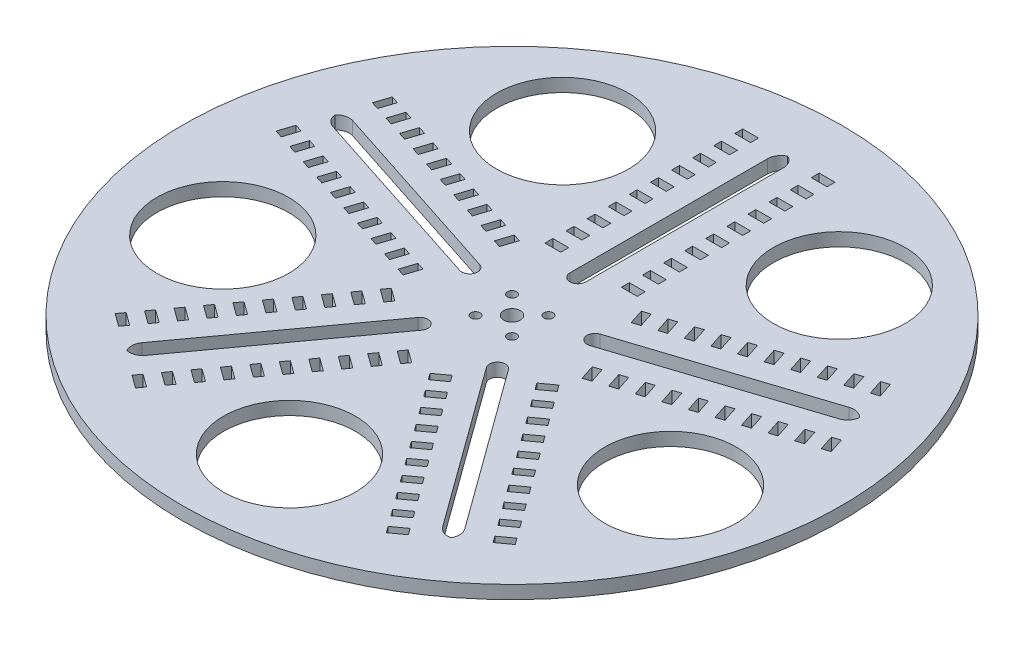
SolidWorks part; units mm, degrees
material "PVC rígido"
ref_plane "Alzado" through (0, 0, 0) normal (0, 0, 1) x (1, 0, 0)
ref_plane "Planta" through (0, 0, 0) normal (0, 1, 0) x (1, 0, 0)
ref_plane "Vista lateral" through (0, 0, 0) normal (1, 0, 0) x (0, 0, -1)
sketch "Croquis1" plane through (0, 0, 0) normal (0, 1, 0) x (1, 0, 0)
  circle A0 centre (0, 0) radius 125
  dimension "D1" = 250
extrude "Saliente-Extruir1" add sketch "Croquis1" along normal blind 5
sketch "Croquis2" plane through (0, 5, 0) normal (0, 1, 0) x (1, 0, 0)
  circle A0 centre (0, 0) radius 3.15
  dimension "D1" = 6.3
extrude "Cortar-Extruir1" cut sketch "Croquis2" against normal through all
sketch "Croquis3" plane through (0, 5, 0) normal (0, 1, 0) x (1, 0, 0)
  line L0 (0, 125) -> (0, -125) construction
  line L1 (-125, 0) -> (125, 0) construction
  line L2 (0, 105) -> (0, 25) construction
  line L3 (3, 105) -> (3, 25)
  line L4 (-3, 105) -> (-3, 25)
  line L5 (99.8609, 32.4468) -> (23.7764, 7.7254) construction
  line L6 (100.788, 29.5936) -> (24.7035, 4.8723)
  line L7 (98.9339, 35.3) -> (22.8494, 10.5786)
  line L8 (61.7175, -84.9468) -> (14.6946, -20.2254) construction
  line L9 (59.2904, -86.7101) -> (12.2676, -21.9888)
  line L10 (64.1445, -83.1834) -> (17.1217, -18.4621)
  line L11 (-61.7175, -84.9468) -> (-14.6946, -20.2254) construction
  line L12 (-64.1445, -83.1834) -> (-17.1217, -18.4621)
  line L13 (-59.2904, -86.7101) -> (-12.2676, -21.9888)
  line L14 (-99.8609, 32.4468) -> (-23.7764, 7.7254) construction
  line L15 (-98.9339, 35.3) -> (-22.8494, 10.5786)
  line L16 (-100.788, 29.5936) -> (-24.7035, 4.8723)
  circle A0 centre (0, 0) radius 105
  circle A1 centre (0, 0) radius 125 construction
  arc A2 (3, 105) -> (-3, 105) centre (0, 105) ccw
  arc A3 (-3, 25) -> (3, 25) centre (0, 25) ccw
  arc A4 (100.788, 29.5936) -> (98.9339, 35.3) centre (99.8609, 32.4468) ccw
  arc A5 (22.8494, 10.5786) -> (24.7035, 4.8723) centre (23.7764, 7.7254) ccw
  arc A6 (59.2904, -86.7101) -> (64.1445, -83.1834) centre (61.7175, -84.9468) ccw
  arc A7 (17.1217, -18.4621) -> (12.2676, -21.9888) centre (14.6946, -20.2254) ccw
  arc A8 (-64.1445, -83.1834) -> (-59.2904, -86.7101) centre (-61.7175, -84.9468) ccw
  arc A9 (-12.2676, -21.9888) -> (-17.1217, -18.4621) centre (-14.6946, -20.2254) ccw
  arc A10 (-98.9339, 35.3) -> (-100.788, 29.5936) centre (-99.8609, 32.4468) ccw
  arc A11 (-24.7035, 4.8723) -> (-22.8494, 10.5786) centre (-23.7764, 7.7254) ccw
  point P12 (0, 65)
  point P22 (61.8187, 20.0861)
  point P29 (38.206, -52.5861)
  point P36 (-38.206, -52.5861)
  point P43 (-61.8187, 20.0861)
  point P48 (0, 0)
  dimension "D1" = 210
  dimension "D3" = 3
  dimension "D2" = 80
  dimension "D4" = 5
extrude "Cortar-Extruir2" cut sketch "Croquis3" against normal through all contours L4 A3 L3 A0 | L7 A5 L6 A0 | L10 A7 L9 A0 | L13 A9 L12 A0 | L16 A11 L15 A0 region at (0, 5, -63.812) region at (60.6889, 5, -19.719) region at (-60.6889, 5, -19.719) region at (37.5078, 5, 51.625) region at (-37.5078, 5, 51.625)
sketch "Croquis5" plane through (0, 5, 0) normal (0, 1, 0) x (1, 0, 0)
  line L0 (0, 125) -> (0, -125) construction
  line L1 (-60.6817, 105) -> (53.5171, 105) construction
  line L2 (91.6, 48.1632) -> (93.4541, 42.4569)
  line L3 (-17.5, 105) -> (-11.5, 105)
  line L4 (-17.5, 105) -> (-17.5, 102)
  line L5 (-17.5, 102) -> (-11.5, 102)
  line L6 (-11.5, 105) -> (-11.5, 102)
  line L7 (11.5, 105) -> (17.5, 105)
  line L8 (11.5, 105) -> (11.5, 102)
  line L9 (11.5, 102) -> (17.5, 102)
  line L10 (17.5, 105) -> (17.5, 102)
  line L11 (100.5615, 20.5826) -> (102.4156, 14.8762)
  line L12 (94.4531, 49.0903) -> (91.6, 48.1632)
  line L13 (94.4531, 49.0903) -> (96.3072, 43.3839)
  line L14 (96.3072, 43.3839) -> (93.4541, 42.4569)
  line L15 (103.4146, 21.5096) -> (100.5615, 20.5826)
  line L16 (103.4146, 21.5096) -> (105.2687, 15.8033)
  line L17 (105.2687, 15.8033) -> (102.4156, 14.8762)
  line L18 (74.1119, -72.2335) -> (69.2578, -75.7602)
  line L19 (50.6504, -89.2793) -> (45.7963, -92.806)
  line L20 (75.8752, -74.6605) -> (74.1119, -72.2335)
  line L21 (75.8752, -74.6605) -> (71.0211, -78.1873)
  line L22 (71.0211, -78.1873) -> (69.2578, -75.7602)
  line L23 (52.4138, -91.7063) -> (50.6504, -89.2793)
  line L24 (52.4138, -91.7063) -> (47.5597, -95.233)
  line L25 (47.5597, -95.233) -> (45.7963, -92.806)
  line L26 (-45.7963, -92.806) -> (-50.6504, -89.2793)
  line L27 (-69.2578, -75.7602) -> (-74.1119, -72.2335)
  line L28 (-47.5597, -95.233) -> (-45.7963, -92.806)
  line L29 (-47.5597, -95.233) -> (-52.4138, -91.7063)
  line L30 (-52.4138, -91.7063) -> (-50.6504, -89.2793)
  line L31 (-71.0211, -78.1873) -> (-69.2578, -75.7602)
  line L32 (-71.0211, -78.1873) -> (-75.8752, -74.6605)
  line L33 (-75.8752, -74.6605) -> (-74.1119, -72.2335)
  line L34 (-102.4156, 14.8762) -> (-100.5615, 20.5826)
  line L35 (-93.4541, 42.4569) -> (-91.6, 48.1632)
  line L36 (-105.2687, 15.8033) -> (-102.4156, 14.8762)
  line L37 (-105.2687, 15.8033) -> (-103.4146, 21.5096)
  line L38 (-103.4146, 21.5096) -> (-100.5615, 20.5826)
  line L39 (-96.3072, 43.3839) -> (-93.4541, 42.4569)
  line L40 (-96.3072, 43.3839) -> (-94.4531, 49.0903)
  line L41 (-94.4531, 49.0903) -> (-91.6, 48.1632)
  circle A0 centre (0, 0) radius 125 construction
  point P50 (0, 0)
  dimension "D1" = 20
  dimension "D2" = 6
  dimension "D3" = 3
  dimension "D4" = 11.5
  dimension "D5" = 6
  dimension "D6" = 3
  dimension "D7" = 11.5
  dimension "D8" = 5
extrude "Cortar-Extruir3" cut sketch "Croquis5" against normal through all
sketch "Croquis7" plane through (0, 5, 0) normal (0, 1, 0) x (1, 0, 0)
  line L0 (-98.8931, 35.2867) -> (-3, 104.9571) construction
  circle A0 centre (-50.9466, 70.1219) radius 25
  circle A1 centre (52.2378, 71.8992) radius 25
  circle A2 centre (85.8139, -25.6858) radius 25
  circle A3 centre (3.3806, -87.7739) radius 25
  circle A4 centre (-81.142, -28.5615) radius 25
  point P16 (1.8687, 0)
  dimension "D1" = 50
  dimension "D2" = 5
extrude "Cortar-Extruir4" cut sketch "Croquis7" against normal blind 10
fillet "Redondeo1" radius 5 10 edges at (-98.8931, 2.5, -35.2867) (-100.7472, 2.5, -29.5804) (-64.1193, 2.5, 83.1487) (-59.2652, 2.5, 86.6755) (59.2652, 2.5, 86.6755) (64.1193, 2.5, 83.1487) (100.7472, 2.5, -29.5804) (98.8931, 2.5, -35.2867) (3, 2.5, -104.9571) (-3, 2.5, -104.9571)
sketch "Croquis8" plane through (0, 5, 0) normal (0, 1, 0) x (1, 0, 0)
  line L1 (-6.915, 6.915) -> (6.915, 6.915)
  line L2 (-6.915, 6.915) -> (-6.915, -6.915)
  line L3 (-6.915, -6.915) -> (6.915, -6.915)
  line L4 (6.915, 6.915) -> (6.915, -6.915)
  line L5 (-6.915, 6.915) -> (6.915, -6.915) construction
  line L6 (-6.915, -6.915) -> (6.915, 6.915) construction
  circle A0 centre (-6.915, 6.915) radius 1.75
  circle A1 centre (6.915, 6.915) radius 1.75
  circle A2 centre (6.915, -6.915) radius 1.75
  circle A3 centre (-6.915, -6.915) radius 1.75
  point P0 (0, 0)
  dimension "D3" = 3.5
  dimension "D4" = 3.5
  dimension "D5" = 3.5
  dimension "D6" = 3.5
  dimension "D1" = 13.83
  dimension "D2" = 13.83
extrude "Cortar-Extruir5" cut sketch "Croquis8" against normal through all contours L1 A0 L2 | L2 A0 L1 | L4 A1 L1 | L1 A1 L4 | L3 A2 L4 | L4 A2 L3 | L2 A3 L3 | L3 A3 L2 region at (-7.1626, 5, -7.1626) region at (-6.1723, 5, -6.1723) region at (7.1626, 5, -7.1626) region at (6.1723, 5, -6.1723) region at (-6.1723, 5, 6.1723) region at (-7.1626, 5, 7.1626) region at (7.1626, 5, 7.1626) region at (6.1723, 5, 6.1723)
sketch "Croquis9" plane through (0, 5, 0) normal (0, 1, 0) x (1, 0, 0)
  line L0 (0, 104.5626) -> (0, 0) construction
  line L1 (-17.5, 97) -> (-11.5, 97)
  line L2 (-17.5, 97) -> (-17.5, 94)
  line L3 (-17.5, 94) -> (-11.5, 94)
  line L4 (-11.5, 97) -> (-11.5, 94)
  line L5 (-17.5, 97) -> (-11.5, 94) construction
  line L6 (-17.5, 94) -> (-11.5, 97) construction
  line L7 (11.5, 97) -> (17.5, 97)
  line L8 (11.5, 97) -> (11.5, 94)
  line L9 (11.5, 94) -> (17.5, 94)
  line L10 (17.5, 97) -> (17.5, 94)
  line L11 (11.5, 97) -> (17.5, 94) construction
  line L12 (11.5, 94) -> (17.5, 97) construction
  line L13 (-17.5, 102) -> (-11.5, 102) construction
  line L14 (11.5, 102) -> (17.5, 102) construction
  line L15 (-17.5, 89) -> (-11.5, 89)
  line L16 (-17.5, 89) -> (-17.5, 86)
  line L17 (-17.5, 86) -> (-11.5, 86)
  line L18 (-11.5, 89) -> (-11.5, 86)
  line L19 (11.5, 89) -> (11.5, 86)
  line L20 (11.5, 89) -> (17.5, 89)
  line L21 (11.5, 86) -> (17.5, 86)
  line L22 (17.5, 89) -> (17.5, 86)
  line L23 (-17.5, 81) -> (-11.5, 81)
  line L24 (-17.5, 81) -> (-17.5, 78)
  line L25 (-17.5, 78) -> (-11.5, 78)
  line L26 (-11.5, 81) -> (-11.5, 78)
  line L27 (11.5, 81) -> (11.5, 78)
  line L28 (11.5, 81) -> (17.5, 81)
  line L29 (11.5, 78) -> (17.5, 78)
  line L30 (17.5, 81) -> (17.5, 78)
  line L31 (-17.5, 73) -> (-11.5, 73)
  line L32 (-17.5, 73) -> (-17.5, 70)
  line L33 (-17.5, 70) -> (-11.5, 70)
  line L34 (-11.5, 73) -> (-11.5, 70)
  line L35 (11.5, 73) -> (11.5, 70)
  line L36 (11.5, 73) -> (17.5, 73)
  line L37 (11.5, 70) -> (17.5, 70)
  line L38 (17.5, 73) -> (17.5, 70)
  line L39 (-17.5, 65) -> (-11.5, 65)
  line L40 (-17.5, 65) -> (-17.5, 62)
  line L41 (-17.5, 62) -> (-11.5, 62)
  line L42 (-11.5, 65) -> (-11.5, 62)
  line L43 (11.5, 65) -> (11.5, 62)
  line L44 (11.5, 65) -> (17.5, 65)
  line L45 (11.5, 62) -> (17.5, 62)
  line L46 (17.5, 65) -> (17.5, 62)
  line L47 (-17.5, 57) -> (-11.5, 57)
  line L48 (-17.5, 57) -> (-17.5, 54)
  line L49 (-17.5, 54) -> (-11.5, 54)
  line L50 (-11.5, 57) -> (-11.5, 54)
  line L51 (11.5, 57) -> (11.5, 54)
  line L52 (11.5, 57) -> (17.5, 57)
  line L53 (11.5, 54) -> (17.5, 54)
  line L54 (17.5, 57) -> (17.5, 54)
  line L55 (-17.5, 49) -> (-11.5, 49)
  line L56 (-17.5, 49) -> (-17.5, 46)
  line L57 (-17.5, 46) -> (-11.5, 46)
  line L58 (-11.5, 49) -> (-11.5, 46)
  line L59 (11.5, 49) -> (11.5, 46)
  line L60 (11.5, 49) -> (17.5, 49)
  line L61 (11.5, 46) -> (17.5, 46)
  line L62 (17.5, 49) -> (17.5, 46)
  line L63 (-17.5, 41) -> (-11.5, 41)
  line L64 (-17.5, 41) -> (-17.5, 38)
  line L65 (-17.5, 38) -> (-11.5, 38)
  line L66 (-11.5, 41) -> (-11.5, 38)
  line L67 (11.5, 41) -> (11.5, 38)
  line L68 (11.5, 41) -> (17.5, 41)
  line L69 (11.5, 38) -> (17.5, 38)
  line L70 (17.5, 41) -> (17.5, 38)
  line L71 (-17.5, 33) -> (-11.5, 33)
  line L72 (-17.5, 33) -> (-17.5, 30)
  line L73 (-17.5, 30) -> (-11.5, 30)
  line L74 (-11.5, 33) -> (-11.5, 30)
  line L75 (11.5, 33) -> (11.5, 30)
  line L76 (11.5, 33) -> (17.5, 33)
  line L77 (11.5, 30) -> (17.5, 30)
  line L78 (17.5, 33) -> (17.5, 30)
  line L79 (86.8447, 46.6181) -> (88.6988, 40.9118)
  line L80 (86.8447, 46.6181) -> (83.9915, 45.6911)
  line L81 (83.9915, 45.6911) -> (85.8456, 39.9847)
  line L82 (88.6988, 40.9118) -> (85.8456, 39.9847)
  line L83 (95.8062, 19.0375) -> (92.953, 18.1104)
  line L84 (95.8062, 19.0375) -> (97.6603, 13.3312)
  line L85 (97.6603, 13.3312) -> (94.8071, 12.4041)
  line L86 (92.953, 18.1104) -> (94.8071, 12.4041)
  line L87 (71.173, -68.1884) -> (66.3189, -71.7151)
  line L88 (71.173, -68.1884) -> (69.4096, -65.7614)
  line L89 (69.4096, -65.7614) -> (64.5555, -69.2881)
  line L90 (66.3189, -71.7151) -> (64.5555, -69.2881)
  line L91 (47.7115, -85.2342) -> (45.9481, -82.8071)
  line L92 (47.7115, -85.2342) -> (42.8574, -88.7609)
  line L93 (42.8574, -88.7609) -> (41.094, -86.3338)
  line L94 (45.9481, -82.8071) -> (41.094, -86.3338)
  line L95 (-42.8574, -88.7609) -> (-47.7115, -85.2342)
  line L96 (-42.8574, -88.7609) -> (-41.094, -86.3338)
  line L97 (-41.094, -86.3338) -> (-45.9481, -82.8071)
  line L98 (-47.7115, -85.2342) -> (-45.9481, -82.8071)
  line L99 (-66.3189, -71.7151) -> (-64.5555, -69.2881)
  line L100 (-66.3189, -71.7151) -> (-71.173, -68.1884)
  line L101 (-71.173, -68.1884) -> (-69.4096, -65.7614)
  line L102 (-64.5555, -69.2881) -> (-69.4096, -65.7614)
  line L103 (-97.6603, 13.3312) -> (-95.8062, 19.0375)
  line L104 (-97.6603, 13.3312) -> (-94.8071, 12.4041)
  line L105 (-94.8071, 12.4041) -> (-92.953, 18.1104)
  line L106 (-95.8062, 19.0375) -> (-92.953, 18.1104)
  line L107 (-88.6988, 40.9118) -> (-85.8456, 39.9847)
  line L108 (-88.6988, 40.9118) -> (-86.8447, 46.6181)
  line L109 (-86.8447, 46.6181) -> (-83.9915, 45.6911)
  line L110 (-85.8456, 39.9847) -> (-83.9915, 45.6911)
  line L111 (73.4819, 35.9675) -> (70.6287, 35.0405)
  line L112 (71.6278, 41.6739) -> (73.4819, 35.9675)
  line L113 (71.6278, 41.6739) -> (68.7746, 40.7468)
  line L114 (68.7746, 40.7468) -> (70.6287, 35.0405)
  line L115 (80.5893, 14.0932) -> (82.4434, 8.3869)
  line L116 (82.4434, 8.3869) -> (79.5902, 7.4598)
  line L117 (77.7361, 13.1662) -> (79.5902, 7.4598)
  line L118 (80.5893, 14.0932) -> (77.7361, 13.1662)
  line L119 (56.9143, -58.7708) -> (55.1509, -56.3438)
  line L120 (61.7684, -55.2441) -> (56.9143, -58.7708)
  line L121 (61.7684, -55.2441) -> (60.005, -52.8171)
  line L122 (60.005, -52.8171) -> (55.1509, -56.3438)
  line L123 (38.3069, -72.2899) -> (33.4528, -75.8166)
  line L124 (33.4528, -75.8166) -> (31.6895, -73.3896)
  line L125 (36.5436, -69.8629) -> (31.6895, -73.3896)
  line L126 (38.3069, -72.2899) -> (36.5436, -69.8629)
  line L127 (-38.3069, -72.2899) -> (-36.5436, -69.8629)
  line L128 (-33.4528, -75.8166) -> (-38.3069, -72.2899)
  line L129 (-33.4528, -75.8166) -> (-31.6895, -73.3896)
  line L130 (-31.6895, -73.3896) -> (-36.5436, -69.8629)
  line L131 (-56.9143, -58.7708) -> (-61.7684, -55.2441)
  line L132 (-61.7684, -55.2441) -> (-60.005, -52.8171)
  line L133 (-55.1509, -56.3438) -> (-60.005, -52.8171)
  line L134 (-56.9143, -58.7708) -> (-55.1509, -56.3438)
  line L135 (-80.5893, 14.0932) -> (-77.7361, 13.1662)
  line L136 (-82.4434, 8.3869) -> (-80.5893, 14.0932)
  line L137 (-82.4434, 8.3869) -> (-79.5902, 7.4598)
  line L138 (-79.5902, 7.4598) -> (-77.7361, 13.1662)
  line L139 (-73.4819, 35.9675) -> (-71.6278, 41.6739)
  line L140 (-71.6278, 41.6739) -> (-68.7746, 40.7468)
  line L141 (-70.6287, 35.0405) -> (-68.7746, 40.7468)
  line L142 (-73.4819, 35.9675) -> (-70.6287, 35.0405)
  line L143 (79.2362, 44.146) -> (81.0903, 38.4397)
  line L144 (79.2362, 44.146) -> (76.3831, 43.219)
  line L145 (76.3831, 43.219) -> (78.2372, 37.5126)
  line L146 (81.0903, 38.4397) -> (78.2372, 37.5126)
  line L147 (88.1977, 16.5654) -> (85.3446, 15.6383)
  line L148 (88.1977, 16.5654) -> (90.0518, 10.859)
  line L149 (90.0518, 10.859) -> (87.1987, 9.932)
  line L150 (85.3446, 15.6383) -> (87.1987, 9.932)
  line L151 (66.4707, -61.7163) -> (61.6166, -65.243)
  line L152 (66.4707, -61.7163) -> (64.7073, -59.2892)
  line L153 (64.7073, -59.2892) -> (59.8532, -62.8159)
  line L154 (61.6166, -65.243) -> (59.8532, -62.8159)
  line L155 (43.0092, -78.762) -> (41.2458, -76.335)
  line L156 (43.0092, -78.762) -> (38.1551, -82.2888)
  line L157 (38.1551, -82.2888) -> (36.3917, -79.8617)
  line L158 (41.2458, -76.335) -> (36.3917, -79.8617)
  line L159 (-38.1551, -82.2888) -> (-43.0092, -78.762)
  line L160 (-38.1551, -82.2888) -> (-36.3917, -79.8617)
  line L161 (-36.3917, -79.8617) -> (-41.2458, -76.335)
  line L162 (-43.0092, -78.762) -> (-41.2458, -76.335)
  line L163 (-61.6166, -65.243) -> (-59.8532, -62.8159)
  line L164 (-61.6166, -65.243) -> (-66.4707, -61.7163)
  line L165 (-66.4707, -61.7163) -> (-64.7073, -59.2892)
  line L166 (-59.8532, -62.8159) -> (-64.7073, -59.2892)
  line L167 (-90.0518, 10.859) -> (-88.1977, 16.5654)
  line L168 (-90.0518, 10.859) -> (-87.1987, 9.932)
  line L169 (-87.1987, 9.932) -> (-85.3446, 15.6383)
  line L170 (-88.1977, 16.5654) -> (-85.3446, 15.6383)
  line L171 (-81.0903, 38.4397) -> (-78.2372, 37.5126)
  line L172 (-81.0903, 38.4397) -> (-79.2362, 44.146)
  line L173 (-79.2362, 44.146) -> (-76.3831, 43.219)
  line L174 (-78.2372, 37.5126) -> (-76.3831, 43.219)
  line L175 (64.0193, 39.2017) -> (65.8734, 33.4954)
  line L176 (64.0193, 39.2017) -> (61.1662, 38.2747)
  line L177 (61.1662, 38.2747) -> (63.0203, 32.5683)
  line L178 (65.8734, 33.4954) -> (63.0203, 32.5683)
  line L179 (72.9808, 11.6211) -> (74.8349, 5.9148)
  line L180 (74.8349, 5.9148) -> (71.9818, 4.9877)
  line L181 (72.9808, 11.6211) -> (70.1277, 10.694)
  line L182 (70.1277, 10.694) -> (71.9818, 4.9877)
  line L183 (57.0661, -48.772) -> (52.212, -52.2987)
  line L184 (57.0661, -48.772) -> (55.3028, -46.3449)
  line L185 (55.3028, -46.3449) -> (50.4487, -49.8717)
  line L186 (52.212, -52.2987) -> (50.4487, -49.8717)
  line L187 (33.6046, -65.8178) -> (28.7505, -69.3445)
  line L188 (28.7505, -69.3445) -> (26.9872, -66.9174)
  line L189 (33.6046, -65.8178) -> (31.8413, -63.3907)
  line L190 (31.8413, -63.3907) -> (26.9872, -66.9174)
  line L191 (-28.7505, -69.3445) -> (-33.6046, -65.8178)
  line L192 (-28.7505, -69.3445) -> (-26.9872, -66.9174)
  line L193 (-26.9872, -66.9174) -> (-31.8413, -63.3907)
  line L194 (-33.6046, -65.8178) -> (-31.8413, -63.3907)
  line L195 (-52.212, -52.2987) -> (-57.0661, -48.772)
  line L196 (-57.0661, -48.772) -> (-55.3028, -46.3449)
  line L197 (-52.212, -52.2987) -> (-50.4487, -49.8717)
  line L198 (-50.4487, -49.8717) -> (-55.3028, -46.3449)
  line L199 (-74.8349, 5.9148) -> (-72.9808, 11.6211)
  line L200 (-74.8349, 5.9148) -> (-71.9818, 4.9877)
  line L201 (-71.9818, 4.9877) -> (-70.1277, 10.694)
  line L202 (-72.9808, 11.6211) -> (-70.1277, 10.694)
  line L203 (-65.8734, 33.4954) -> (-64.0193, 39.2017)
  line L204 (-64.0193, 39.2017) -> (-61.1662, 38.2747)
  line L205 (-65.8734, 33.4954) -> (-63.0203, 32.5683)
  line L206 (-63.0203, 32.5683) -> (-61.1662, 38.2747)
  line L207 (48.8024, 34.2575) -> (50.6565, 28.5511)
  line L208 (48.8024, 34.2575) -> (45.9493, 33.3304)
  line L209 (45.9493, 33.3304) -> (47.8034, 27.6241)
  line L210 (50.6565, 28.5511) -> (47.8034, 27.6241)
  line L211 (57.7639, 6.6768) -> (54.9107, 5.7498)
  line L212 (57.7639, 6.6768) -> (59.618, 0.9705)
  line L213 (59.618, 0.9705) -> (56.7648, 0.0434)
  line L214 (54.9107, 5.7498) -> (56.7648, 0.0434)
  line L215 (47.6616, -35.8277) -> (42.8075, -39.3544)
  line L216 (47.6616, -35.8277) -> (45.8982, -33.4007)
  line L217 (45.8982, -33.4007) -> (41.0441, -36.9274)
  line L218 (42.8075, -39.3544) -> (41.0441, -36.9274)
  line L219 (24.2001, -52.8735) -> (22.4367, -50.4464)
  line L220 (24.2001, -52.8735) -> (19.346, -56.4002)
  line L221 (19.346, -56.4002) -> (17.5826, -53.9732)
  line L222 (22.4367, -50.4464) -> (17.5826, -53.9732)
  line L223 (-19.346, -56.4002) -> (-24.2001, -52.8735)
  line L224 (-19.346, -56.4002) -> (-17.5826, -53.9732)
  line L225 (-17.5826, -53.9732) -> (-22.4367, -50.4464)
  line L226 (-24.2001, -52.8735) -> (-22.4367, -50.4464)
  line L227 (-42.8075, -39.3544) -> (-41.0441, -36.9274)
  line L228 (-42.8075, -39.3544) -> (-47.6616, -35.8277)
  line L229 (-47.6616, -35.8277) -> (-45.8982, -33.4007)
  line L230 (-41.0441, -36.9274) -> (-45.8982, -33.4007)
  line L231 (-59.618, 0.9705) -> (-57.7639, 6.6768)
  line L232 (-59.618, 0.9705) -> (-56.7648, 0.0434)
  line L233 (-56.7648, 0.0434) -> (-54.9107, 5.7498)
  line L234 (-57.7639, 6.6768) -> (-54.9107, 5.7498)
  line L235 (-50.6565, 28.5511) -> (-47.8034, 27.6241)
  line L236 (-50.6565, 28.5511) -> (-48.8024, 34.2575)
  line L237 (-48.8024, 34.2575) -> (-45.9493, 33.3304)
  line L238 (-47.8034, 27.6241) -> (-45.9493, 33.3304)
  line L239 (56.4109, 36.7296) -> (58.265, 31.0233)
  line L240 (56.4109, 36.7296) -> (53.5577, 35.8025)
  line L241 (58.265, 31.0233) -> (55.4118, 30.0962)
  line L242 (53.5577, 35.8025) -> (55.4118, 30.0962)
  line L243 (65.3724, 9.149) -> (67.2265, 3.4426)
  line L244 (67.2265, 3.4426) -> (64.3733, 2.5156)
  line L245 (65.3724, 9.149) -> (62.5192, 8.2219)
  line L246 (62.5192, 8.2219) -> (64.3733, 2.5156)
  line L247 (52.3638, -42.2999) -> (47.5097, -45.8266)
  line L248 (52.3638, -42.2999) -> (50.6005, -39.8728)
  line L249 (47.5097, -45.8266) -> (45.7464, -43.3995)
  line L250 (50.6005, -39.8728) -> (45.7464, -43.3995)
  line L251 (28.9023, -59.3456) -> (24.0482, -62.8723)
  line L252 (24.0482, -62.8723) -> (22.2849, -60.4453)
  line L253 (28.9023, -59.3456) -> (27.139, -56.9186)
  line L254 (27.139, -56.9186) -> (22.2849, -60.4453)
  line L255 (-24.0482, -62.8723) -> (-28.9023, -59.3456)
  line L256 (-24.0482, -62.8723) -> (-22.2849, -60.4453)
  line L257 (-28.9023, -59.3456) -> (-27.139, -56.9186)
  line L258 (-22.2849, -60.4453) -> (-27.139, -56.9186)
  line L259 (-47.5097, -45.8266) -> (-52.3638, -42.2999)
  line L260 (-52.3638, -42.2999) -> (-50.6005, -39.8728)
  line L261 (-47.5097, -45.8266) -> (-45.7464, -43.3995)
  line L262 (-45.7464, -43.3995) -> (-50.6005, -39.8728)
  line L263 (-67.2265, 3.4426) -> (-65.3724, 9.149)
  line L264 (-67.2265, 3.4426) -> (-64.3733, 2.5156)
  line L265 (-65.3724, 9.149) -> (-62.5192, 8.2219)
  line L266 (-64.3733, 2.5156) -> (-62.5192, 8.2219)
  line L267 (-58.265, 31.0233) -> (-56.4109, 36.7296)
  line L268 (-56.4109, 36.7296) -> (-53.5577, 35.8025)
  line L269 (-58.265, 31.0233) -> (-55.4118, 30.0962)
  line L270 (-55.4118, 30.0962) -> (-53.5577, 35.8025)
  line L271 (33.5855, 29.3132) -> (35.4396, 23.6068)
  line L272 (33.5855, 29.3132) -> (30.7324, 28.3861)
  line L273 (30.7324, 28.3861) -> (32.5865, 22.6798)
  line L274 (35.4396, 23.6068) -> (32.5865, 22.6798)
  line L275 (42.547, 1.7325) -> (44.4011, -3.9738)
  line L276 (44.4011, -3.9738) -> (41.5479, -4.9008)
  line L277 (42.547, 1.7325) -> (39.6938, 0.8055)
  line L278 (39.6938, 0.8055) -> (41.5479, -4.9008)
  line L279 (38.257, -22.8835) -> (33.4029, -26.4102)
  line L280 (38.257, -22.8835) -> (36.4936, -20.4564)
  line L281 (36.4936, -20.4564) -> (31.6395, -23.9831)
  line L282 (33.4029, -26.4102) -> (31.6395, -23.9831)
  line L283 (14.7955, -39.9292) -> (9.9414, -43.4559)
  line L284 (9.9414, -43.4559) -> (8.178, -41.0289)
  line L285 (14.7955, -39.9292) -> (13.0321, -37.5022)
  line L286 (13.0321, -37.5022) -> (8.178, -41.0289)
  line L287 (-9.9414, -43.4559) -> (-14.7955, -39.9292)
  line L288 (-9.9414, -43.4559) -> (-8.178, -41.0289)
  line L289 (-8.178, -41.0289) -> (-13.0321, -37.5022)
  line L290 (-14.7955, -39.9292) -> (-13.0321, -37.5022)
  line L291 (-33.4029, -26.4102) -> (-38.257, -22.8835)
  line L292 (-38.257, -22.8835) -> (-36.4936, -20.4564)
  line L293 (-33.4029, -26.4102) -> (-31.6395, -23.9831)
  line L294 (-31.6395, -23.9831) -> (-36.4936, -20.4564)
  line L295 (-44.4011, -3.9738) -> (-42.547, 1.7325)
  line L296 (-44.4011, -3.9738) -> (-41.5479, -4.9008)
  line L297 (-41.5479, -4.9008) -> (-39.6938, 0.8055)
  line L298 (-42.547, 1.7325) -> (-39.6938, 0.8055)
  line L299 (-35.4396, 23.6068) -> (-33.5855, 29.3132)
  line L300 (-33.5855, 29.3132) -> (-30.7324, 28.3861)
  line L301 (-35.4396, 23.6068) -> (-32.5865, 22.6798)
  line L302 (-32.5865, 22.6798) -> (-30.7324, 28.3861)
  line L303 (41.194, 31.7853) -> (43.0481, 26.079)
  line L304 (41.194, 31.7853) -> (38.3408, 30.8583)
  line L305 (43.0481, 26.079) -> (40.1949, 25.1519)
  line L306 (38.3408, 30.8583) -> (40.1949, 25.1519)
  line L307 (50.1555, 4.2047) -> (52.0096, -1.5017)
  line L308 (52.0096, -1.5017) -> (49.1564, -2.4287)
  line L309 (50.1555, 4.2047) -> (47.3023, 3.2776)
  line L310 (47.3023, 3.2776) -> (49.1564, -2.4287)
  line L311 (42.9593, -29.3556) -> (38.1052, -32.8823)
  line L312 (42.9593, -29.3556) -> (41.1959, -26.9285)
  line L313 (38.1052, -32.8823) -> (36.3418, -30.4553)
  line L314 (41.1959, -26.9285) -> (36.3418, -30.4553)
  line L315 (19.4978, -46.4014) -> (14.6437, -49.9281)
  line L316 (14.6437, -49.9281) -> (12.8803, -47.501)
  line L317 (19.4978, -46.4014) -> (17.7344, -43.9743)
  line L318 (17.7344, -43.9743) -> (12.8803, -47.501)
  line L319 (-14.6437, -49.9281) -> (-19.4978, -46.4014)
  line L320 (-14.6437, -49.9281) -> (-12.8803, -47.501)
  line L321 (-19.4978, -46.4014) -> (-17.7344, -43.9743)
  line L322 (-12.8803, -47.501) -> (-17.7344, -43.9743)
  line L323 (-38.1052, -32.8823) -> (-42.9593, -29.3556)
  line L324 (-42.9593, -29.3556) -> (-41.1959, -26.9285)
  line L325 (-38.1052, -32.8823) -> (-36.3418, -30.4553)
  line L326 (-36.3418, -30.4553) -> (-41.1959, -26.9285)
  line L327 (-52.0096, -1.5017) -> (-50.1555, 4.2047)
  line L328 (-52.0096, -1.5017) -> (-49.1564, -2.4287)
  line L329 (-50.1555, 4.2047) -> (-47.3023, 3.2776)
  line L330 (-49.1564, -2.4287) -> (-47.3023, 3.2776)
  line L331 (-43.0481, 26.079) -> (-41.194, 31.7853)
  line L332 (-41.194, 31.7853) -> (-38.3408, 30.8583)
  line L333 (-43.0481, 26.079) -> (-40.1949, 25.1519)
  line L334 (-40.1949, 25.1519) -> (-38.3408, 30.8583)
  line L335 (25.9771, 26.841) -> (27.8312, 21.1347)
  line L336 (25.9771, 26.841) -> (23.1239, 25.914)
  line L337 (23.1239, 25.914) -> (24.978, 20.2077)
  line L338 (27.8312, 21.1347) -> (24.978, 20.2077)
  line L339 (34.9386, -0.7396) -> (36.7927, -6.4459)
  line L340 (34.9386, -0.7396) -> (32.0854, -1.6666)
  line L341 (32.0854, -1.6666) -> (33.9395, -7.373)
  line L342 (36.7927, -6.4459) -> (33.9395, -7.373)
  line L343 (33.5547, -16.4113) -> (28.7006, -19.938)
  line L344 (33.5547, -16.4113) -> (31.7914, -13.9843)
  line L345 (31.7914, -13.9843) -> (26.9373, -17.511)
  line L346 (28.7006, -19.938) -> (26.9373, -17.511)
  line L347 (10.0932, -33.4571) -> (5.2391, -36.9838)
  line L348 (10.0932, -33.4571) -> (8.3299, -31.03)
  line L349 (8.3299, -31.03) -> (3.4758, -34.5568)
  line L350 (5.2391, -36.9838) -> (3.4758, -34.5568)
  line L351 (-5.2391, -36.9838) -> (-10.0932, -33.4571)
  line L352 (-5.2391, -36.9838) -> (-3.4758, -34.5568)
  line L353 (-3.4758, -34.5568) -> (-8.3299, -31.03)
  line L354 (-10.0932, -33.4571) -> (-8.3299, -31.03)
  line L355 (-28.7006, -19.938) -> (-33.5547, -16.4113)
  line L356 (-28.7006, -19.938) -> (-26.9373, -17.511)
  line L357 (-26.9373, -17.511) -> (-31.7914, -13.9843)
  line L358 (-33.5547, -16.4113) -> (-31.7914, -13.9843)
  line L359 (-36.7927, -6.4459) -> (-34.9386, -0.7396)
  line L360 (-36.7927, -6.4459) -> (-33.9395, -7.373)
  line L361 (-33.9395, -7.373) -> (-32.0854, -1.6666)
  line L362 (-34.9386, -0.7396) -> (-32.0854, -1.6666)
  line L363 (-27.8312, 21.1347) -> (-25.9771, 26.841)
  line L364 (-27.8312, 21.1347) -> (-24.978, 20.2077)
  line L365 (-24.978, 20.2077) -> (-23.1239, 25.914)
  line L366 (-25.9771, 26.841) -> (-23.1239, 25.914)
  point P0 (-14.5, 95.5)
  point P5 (14.5, 95.5)
  point P14 (-14.5, 102)
  point P118 (0, 0)
  point P151 (0, 0)
  point P183 (0, 0)
  point P216 (0, 0)
  point P249 (0, 0)
  point P282 (0, 0)
  point P316 (0, 0)
  point P348 (0, 0)
  point P382 (0, 0)
  dimension "D1" = 6
  dimension "D2" = 3
  dimension "D3" = 6
  dimension "D4" = 3
  dimension "D5" = 11.5
  dimension "D6" = 11.5
  dimension "D7" = 5
  dimension "D8" = 5
  dimension "D9" = 9
  dimension "D10" = 5
  dimension "D11" = 5
  dimension "D12" = 5
  dimension "D13" = 5
  dimension "D14" = 5
  dimension "D15" = 5
  dimension "D16" = 5
  dimension "D17" = 5
  dimension "D18" = 5
extrude "Cortar-Extruir6" cut sketch "Croquis9" against normal through all
